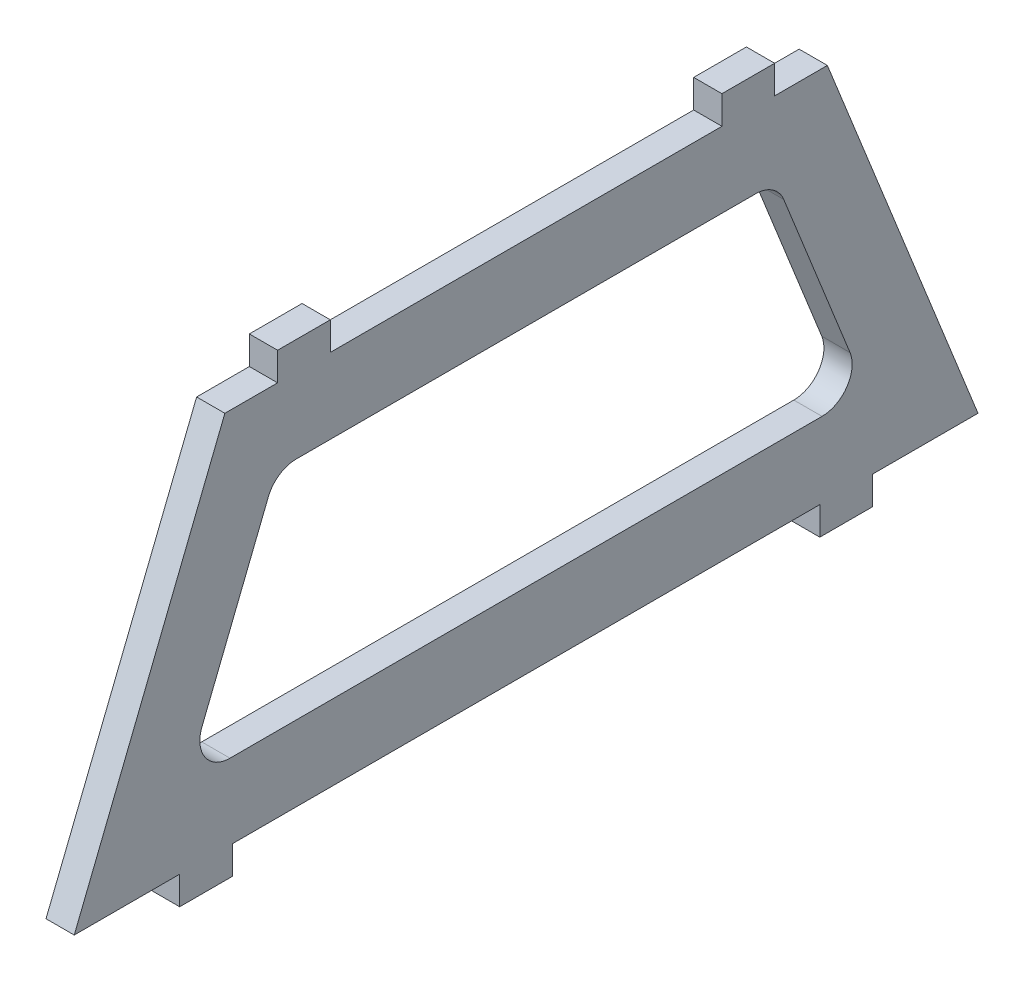
SolidWorks part; units mm, degrees
ref_plane "Front Plane" through (0, 0, 0) normal (0, 0, 1) x (1, 0, 0)
ref_plane "Top Plane" through (0, 0, 0) normal (0, 1, 0) x (1, 0, 0)
ref_plane "Right Plane" through (0, 0, 0) normal (1, 0, 0) x (0, 0, -1)
sketch "Sketch1" plane through (0, 0, 0) normal (1, 0, 0) x (0, 0, -1)
  line L0 (-101.6, 63.5) -> (-127, 0)
  line L1 (0, 0) -> (-101.6, 0)
  line L3 (0, 63.5) -> (-101.6, 63.5)
  line L5 (-127, 0) -> (-101.6, 0)
  line L6 (-50.8, 63.5) -> (-50.8, 52.984) construction
  line L7 (25.4, 0) -> (0, 0)
  line L8 (0, 63.5) -> (25.4, 0)
  line L9 (7.62, -4.7625) -> (-1.27, -4.7625)
  line L10 (-92.71, 63.5) -> (-83.82, 63.5)
  line L11 (-92.71, 63.5) -> (-92.71, 68.2625)
  line L12 (-92.71, 68.2625) -> (-83.82, 68.2625)
  line L13 (-83.82, 63.5) -> (-83.82, 68.2625)
  line L14 (-109.22, 0) -> (-100.33, 0)
  line L15 (-109.22, 0) -> (-109.22, -4.7625)
  line L16 (-109.22, -4.7625) -> (-100.33, -4.7625)
  line L17 (-100.33, 0) -> (-100.33, -4.7625)
  line L18 (-1.27, 0) -> (-1.27, -4.7625)
  line L19 (7.62, 0) -> (-1.27, 0)
  line L20 (7.62, 0) -> (7.62, -4.7625)
  line L21 (-8.89, 68.2625) -> (-17.78, 68.2625)
  line L22 (-17.78, 63.5) -> (-17.78, 68.2625)
  line L23 (-8.89, 63.5) -> (-17.78, 63.5)
  line L24 (-8.89, 63.5) -> (-8.89, 68.2625)
  dimension "D1" = 101.6
  dimension "D2" = 63.5
  dimension "D3" = 25.4
  dimension "D4" = 8.89
  dimension "D5" = 8.89
  dimension "D6" = 4.7625
  dimension "D7" = 17.78
  dimension "D8" = 4.7625
  dimension "D9" = 8.89
extrude "Boss-Extrude1" add sketch "Sketch1" along normal blind 4.7625 contours L3 L13 L12 L11 | L3 L24 L21 L22 | L20 L7 L1 L18 L9 | L17 L1 L5 L15 L16 | L8 L3 L0 L5 L1 L7 region at (0, 29.6333, 50.8) region at (0, 65.8812, 88.265) region at (0, -2.3813, 104.775) region at (0, 65.8812, 13.335) region at (0, -2.3813, -3.175)
sketch "Sketch2" plane through (4.7625, 0, 0) normal (1, 0, 0) x (0, 0, -1)
  line L7 (-17.78, 63.5) -> (-83.82, 63.5) construction
  line L8 (-93.0017, 50.8) -> (-8.636, 50.8)
  line L9 (-93.0017, 50.8) -> (-93.0017, 12.7)
  line L10 (-93.0017, 12.7) -> (-8.636, 12.7)
  line L11 (-8.636, 50.8) -> (-8.636, 12.7)
  line L12 (2.6194, 0) -> (-2.6194, 0) construction
  line L13 (-93.0017, 50.8) -> (-108.2417, 12.7)
  line L14 (-108.2417, 12.7) -> (-93.0017, 12.7)
  line L15 (-101.6, 63.5) -> (-127, 0) construction
  line L16 (0, 2.6194) -> (0, -2.6194) construction
  line L17 (-50.8188, 50.8) -> (-50.8188, 44.4795) construction
  line L18 (6.604, 12.7) -> (-8.636, 12.7)
  line L19 (-8.636, 50.8) -> (6.604, 12.7)
  dimension "D1" = 12.7
  dimension "D2" = 12.7
  dimension "D3" = 12.7
  dimension "D4" = 8.636
extrude "Cut-Extrude1" cut sketch "Sketch2" against normal blind 4.7625 contours L13 L14 L9 | L11 L8 L9 L10 | L19 L11 L18 region at (4.7625, 31.75, 50.8188) region at (4.7625, 25.4, 98.0817) region at (4.7625, 25.4, 3.556)
fillet "Fillet1" radius 5.08 4 edges at (2.3813, 12.7, 108.2417) (2.3813, 12.7, -6.604) (2.3813, 50.8, 8.636) (2.3813, 50.8, 93.0017)
